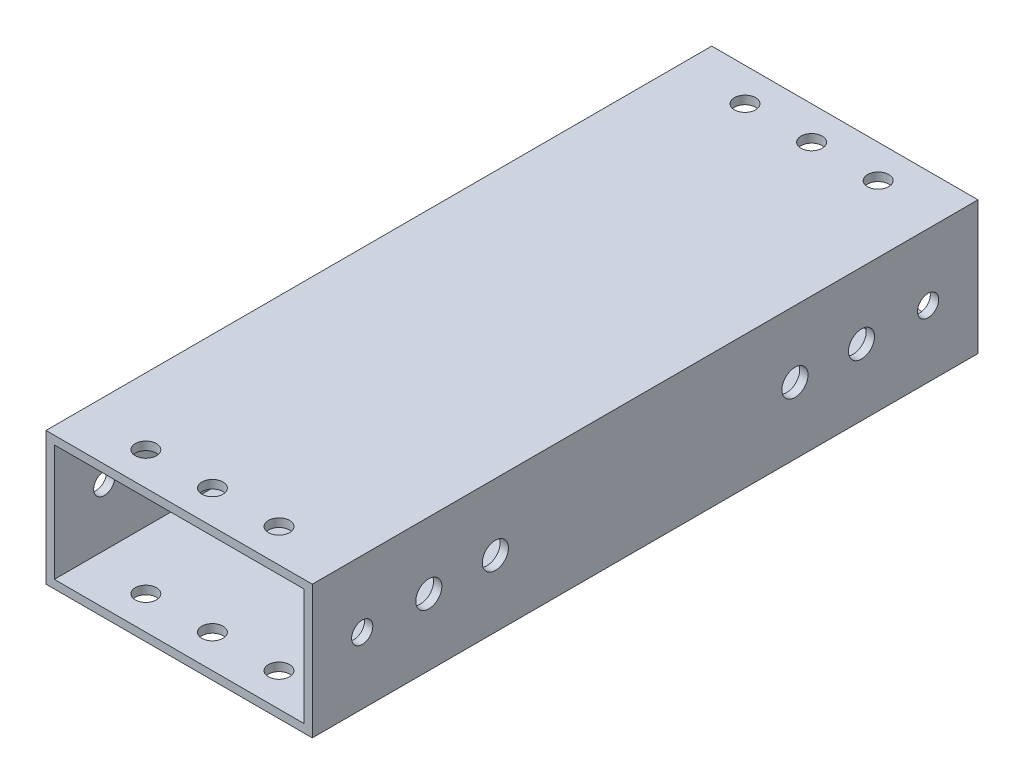
SolidWorks part; units mm, degrees
material "6061-T6 (SS)"
ref_plane "Front Plane" through (0, 0, 0) normal (0, 0, 1) x (1, 0, 0)
ref_plane "Top Plane" through (0, 0, 0) normal (0, 1, 0) x (1, 0, 0)
ref_plane "Right Plane" through (0, 0, 0) normal (1, 0, 0) x (0, 0, -1)
sketch "Sketch1" plane through (0, 0, 0) normal (0, 0, 1) x (1, 0, 0)
  line L0 (-23.8125, 11.1125) -> (23.8125, 11.1125)
  line L1 (-25.4, -12.7) -> (25.4, -12.7)
  line L2 (-25.4, -12.7) -> (-25.4, 12.7)
  line L3 (-25.4, 12.7) -> (25.4, 12.7)
  line L4 (25.4, -12.7) -> (25.4, 12.7)
  line L5 (-25.4, -12.7) -> (25.4, 12.7) construction
  line L6 (-25.4, 12.7) -> (25.4, -12.7) construction
  line L7 (23.8125, -11.1125) -> (23.8125, 11.1125)
  line L8 (-23.8125, -11.1125) -> (23.8125, -11.1125)
  line L9 (-23.8125, -11.1125) -> (-23.8125, 11.1125)
  point P0 (0, 0)
  dimension "D1" = 50.8
  dimension "D2" = 25.4
  dimension "D3" = 1.5875
extrude "Boss-Extrude1" add sketch "Sketch1" along normal mid plane 127
sketch "Sketch2" plane through (0, 12.7, 0) normal (0, 1, 0) x (1, 0, 0)
  line L0 (25.4, 63.5) -> (-25.4, 63.5) construction
  line L1 (25.4, 0) -> (-25.4, 0) construction
  line L2 (25.4, -63.5) -> (25.4, 63.5) construction
  line L3 (-25.4, -63.5) -> (-25.4, 63.5) construction
  circle A0 centre (-12.7, 57.15) radius 2.0193
  circle A1 centre (0, 57.15) radius 2.0193
  circle A2 centre (12.7, 57.15) radius 2.0193
  circle A3 centre (12.7, -57.15) radius 2.0193
  circle A4 centre (0, -57.15) radius 2.0193
  circle A5 centre (-12.7, -57.15) radius 2.0193
  dimension "D1" = 4.0386
  dimension "D2" = 12.7
  dimension "D3" = 12.7
  dimension "D4" = 6.35
extrude "Cut-Extrude1" cut sketch "Sketch2" against normal through all
sketch "Sketch3" plane through (25.4, 0, 0) normal (1, 0, 0) x (0, 0, -1)
  line L0 (0, 12.7) -> (0, -12.7) construction
  line L1 (-63.5, 12.7) -> (63.5, 12.7) construction
  line L2 (-63.5, -12.7) -> (63.5, -12.7) construction
  line L3 (-63.5, -12.7) -> (-63.5, 12.7) construction
  circle A0 centre (-53.975, 0) radius 2.0193
  circle A1 centre (53.975, 0) radius 2.0193
  circle A2 centre (-41.275, 0) radius 2.4892
  circle A3 centre (-28.575, 0) radius 2.4892
  circle A4 centre (28.575, 0) radius 2.4892
  circle A5 centre (41.275, 0) radius 2.4892
  point P17 (0, 0)
  dimension "D1" = 4.0386
  dimension "D3" = 4.9784
  dimension "D2" = 9.525
  dimension "D4" = 12.7
  dimension "D5" = 12.7
extrude "Cut-Extrude2" cut sketch "Sketch3" against normal through all
